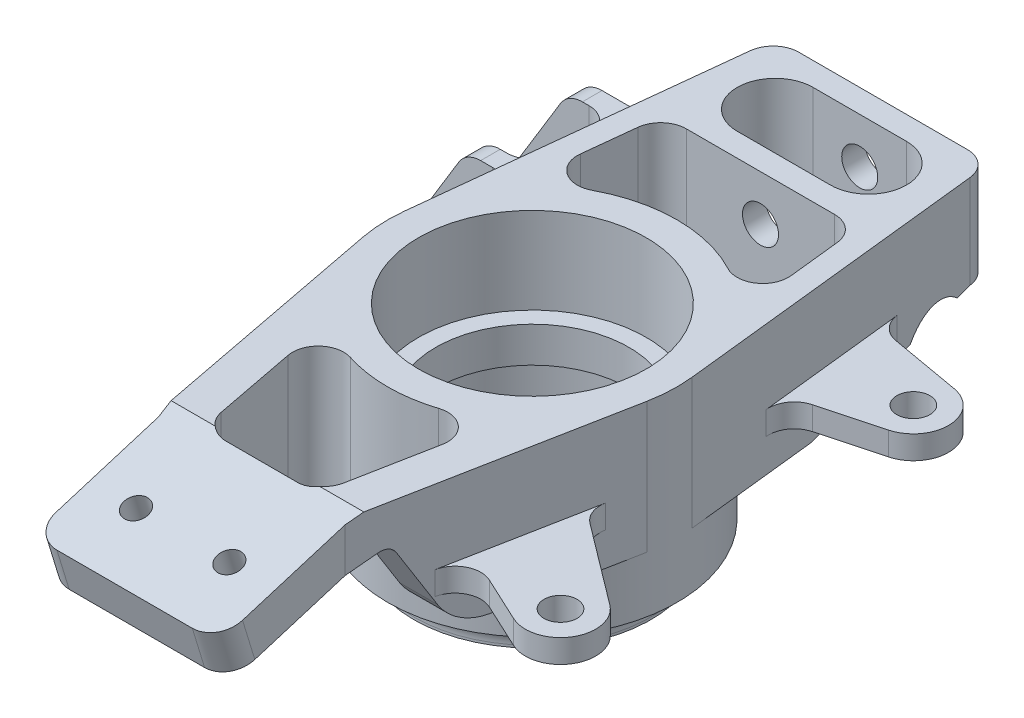
SolidWorks part; units mm, degrees
material "6061-T6 (SS)"
ref_plane "Front Plane" through (0, 0, 0) normal (0, 0, 1) x (1, 0, 0)
ref_plane "Top Plane" through (0, 0, 0) normal (0, 1, 0) x (1, 0, 0)
ref_plane "Right Plane" through (0, 0, 0) normal (1, 0, 0) x (0, 0, -1)
sketch "UBJ LBJ Geometry" plane through (0, 0, 0) normal (1, 0, 0) x (0, 0, -1)
  line L0 (0, 0) -> (0, -97.4059) construction
  line L1 (0, 0) -> (-30.7529, 0) construction
  line L2 (0, 22) -> (-45.5659, 22) construction
  line L3 (0, -10.5425) -> (-23.1063, -10.5425) construction
  line L4 (-84.7344, -51.66) -> (78.74, -22.958) construction
  line L5 (49.4563, 0) -> (49.4563, -88.2735) construction
  circle A0 centre (-84.7344, -51.66) radius 10.3251 construction
  circle A1 centre (78.74, -22.958) radius 10.3251 construction
  dimension "D7" = 20.6502
  dimension "D8" = 20.6502
  dimension "D1" = 22
  dimension "D2" = 32.5425
  dimension "D3" = 44.958
  dimension "D4" = 73.66
  dimension "D5" = 84.7344
  dimension "D6" = 78.74
  dimension "D9" = 29.2837
ref_plane "Wheel Face " through (0, 22, 0) normal (0, -1, 0) x (-1, 0, 0)
ref_plane "Upright Face" through (0, -10.5425, 0) normal (0, -1, 0) x (-1, 0, 0)
ref_plane "Tie Bracket Plane" through (0, 0, -49.4563) normal (0, 0, 1) x (1, 0, 0)
sketch "Tie Bracket Geometry" plane through (0, 0, -49.4563) normal (0, 0, 1) x (1, 0, 0)
  line L0 (0, -28.0995) -> (-60.5599, -51.7108) construction
  line L4 (0, 200000) -> (0, -200097.4059) construction
  circle A0 centre (-60.5599, -51.7108) radius 8.948 construction
  dimension "D1" = 65
  dimension "D2" = 68.7
sketch "Sketch1" plane through (0, 0, 0) normal (0, 0, 1) x (1, 0, 0)
  line L1 (-75.0953, -10.5425) -> (75.0953, -10.5425) construction
  line L2 (-39.37, -10.5425) -> (-39.37, -61.3425)
  line L3 (-39.37, -61.3425) -> (-32.258, -61.3425)
  line L4 (-32.258, -61.3425) -> (-32.258, -68.9625)
  line L5 (-32.258, -68.9625) -> (-30.9829, -68.9625)
  line L8 (-30.9829, -10.5425) -> (-30.9829, -34.0375)
  line L9 (-30.9829, -34.0375) -> (-26.289, -34.0375)
  line L10 (-26.289, -34.0375) -> (-26.289, -43.6895)
  line L11 (-26.289, -43.6895) -> (-30.9829, -43.6895)
  line L12 (-30.9829, -43.6895) -> (-30.9829, -68.9625)
  line L15 (-39.37, -10.5425) -> (-30.9829, -10.5425)
  line L17 (0, 0) -> (0, -23.5057) construction
  dimension "D1" = 9.652
  dimension "D2" = 61.9658
  dimension "D3" = 25.273
  dimension "D4" = 52.578
  dimension "D5" = 23.495
  dimension "D6" = 50.8
  dimension "D7" = 78.74
  dimension "D8" = 64.516
revolve "Bearing Housing Revolve" add sketch "Sketch1" angle 360 about L17
fillet "Bearing Housing Fillet" radius 6.985 1 edges at (0, -61.3425, 32.258)
sketch "Sketch2" plane through (0, -10.5425, 0) normal (0, -1, 0) x (-1, 0, 0)
  line L3 (39.37, -43.18) -> (39.37, 0)
  line L4 (-39.37, -43.18) -> (-39.37, 0)
  line L5 (39.37, -43.18) -> (-39.37, -43.18)
  circle A4 centre (0, 0) radius 39.37 construction
  arc A5 (39.37, 0) -> (-39.37, 0) centre (0, 0) cw
  dimension "D1" = 43.18
extrude "UBJ Prep" add sketch "Sketch2" along normal blind 35.56
sketch "Sketch3" plane through (-39.37, 0, 0) normal (-1, 0, 0) x (0, 0, 1)
  line L0 (-120.7672, 22) -> (120.7672, 22) construction
  line L1 (43.18, -10.5425) -> (72.0727, -10.5425)
  line L2 (72.0727, -10.5425) -> (110.937, -22.4245)
  line L3 (110.937, -22.4245) -> (107.5952, -33.355)
  line L4 (107.5952, -33.355) -> (68.7309, -21.473)
  line L6 (43.18, -46.1025) -> (43.18, -10.5425)
  line L7 (72.0727, -10.5425) -> (68.7309, -21.473) construction
  line L8 (104.3241, 12.415) -> (84.7344, -51.66) construction
  line L9 (55.2328, -39.1959) -> (64.6966, -23.0471)
  circle A0 centre (84.7344, -51.66) radius 12.7 construction
  arc A1 (43.18, -46.1025) -> (55.2328, -39.1959) centre (43.18, -32.1325) ccw
  arc A2 (68.7309, -21.473) -> (64.6966, -23.0471) centre (67.7098, -24.8129) ccw
  dimension "D7" = 6.985
  dimension "D8" = 27.94
  dimension "D9" = 25.4
  dimension "D1" = 73.66
  dimension "D2" = 84.7344
  dimension "D3" = 11.43
  dimension "D4" = 40.64
  dimension "D5" = 17
  dimension "D6" = 16.51
extrude "UBJ Extrude " add sketch "Sketch3" against normal up to surface (78.74 mm away) up to face at (39.37, -28.3225, 21.59)
sketch "Sketch4" plane through (0, -0.4206, -0.1286) normal (0, -0.9563, -0.2924) x (1, 0, 0)
  line L0 (0, 112.6458) -> (0, 27.8969) construction
  line L1 (39.37, 112.6458) -> (-39.37, 112.6458) construction
  line L3 (-12.7, 96.1358) -> (12.7, 96.1358) construction
  circle A0 centre (-12.7, 96.1358) radius 3.2639
  circle A1 centre (12.7, 96.1358) radius 3.2639
  point P8 (0, 96.1358)
  dimension "D2" = 6.5278
  dimension "D1" = 25.4
extrude "Camber Block Holes" cut sketch "Sketch4" against normal up to surface (11.43 mm away) up to face at (0, -16.4835, 91.5049)
sketch "Sketch5" plane through (0, -46.1025, 0) normal (0, -1, 0) x (1, 0, 0)
  line L0 (-25.4, 107.5952) -> (-25.4, 76.3532)
  line L1 (25.4, 110.937) -> (39.37, 110.937)
  line L2 (39.37, 107.5952) -> (-39.37, 107.5952) construction
  line L4 (-25.4, 76.3532) -> (-38.6608, 7.4393)
  line L5 (25.4, 107.5952) -> (25.4, 76.3532)
  line L6 (25.4, 76.3532) -> (38.6608, 7.4393)
  line L7 (-25.4, 107.5952) -> (-25.4, 110.937)
  line L8 (39.37, 110.937) -> (-39.37, 110.937) construction
  line L9 (25.4, 107.5952) -> (25.4, 110.937)
  line L10 (-25.4, 110.937) -> (-39.37, 110.937)
  line L11 (-39.37, 110.937) -> (-39.37, 0)
  line L12 (39.37, 110.937) -> (39.37, 0)
  line L13 (-15.5718, 73.66) -> (15.5718, 73.66)
  line L14 (-15.5718, 73.66) -> (-23.6959, 31.4404)
  line L15 (15.5718, 73.66) -> (23.6959, 31.4404)
  arc A0 (-39.37, 0) -> (-38.6608, 7.4393) centre (0, 0) cw
  circle A1 centre (0, 0) radius 39.37 construction
  arc A2 (39.37, 0) -> (-39.37, 0) centre (0, 0) ccw construction
  arc A3 (39.37, 0) -> (38.6608, 7.4393) centre (0, 0) ccw
  arc A4 (-23.6959, 31.4404) -> (23.6959, 31.4404) centre (0, 0) cw
  point P31 (0, 73.66)
  dimension "D1" = 25.4
  dimension "D2" = 10.16
  dimension "D3" = 31.242
  dimension "D4" = 73.66
extrude "Weight Saving" cut sketch "Sketch5" against normal through all
fillet "Fillet2" radius 6.985 4 edges at (23.6959, -28.3225, 31.4404) (-23.6959, -28.3225, 31.4404) (15.5718, -17.0039, 73.66) (-15.5718, -17.0039, 73.66)
sketch "Sketch6" plane through (0, -10.5425, 0) normal (0, -1, 0) x (-1, 0, 0)
  line L0 (-39.37, 0) -> (-39.37, 40.64)
  line L1 (-39.37, 40.64) -> (39.37, 40.64)
  line L2 (39.37, 40.64) -> (39.37, 0)
  circle A0 centre (0, 0) radius 39.37 construction
  arc A1 (-39.37, 0) -> (39.37, 0) centre (0, 0) cw
  dimension "D1" = 40.64
extrude "LBJ Prep" add sketch "Sketch6" along normal blind 35.56
sketch "Sketch8" plane through (-39.37, 0, 0) normal (-1, 0, 0) x (0, 0, 1)
  line L0 (-40.64, -10.5425) -> (-95.4151, -10.5425)
  line L1 (-95.4151, -10.5425) -> (-95.4151, -35.9425)
  line L2 (-95.4151, -35.9425) -> (-89.0651, -35.9425)
  line L7 (-40.64, -46.1025) -> (-40.64, -10.5425)
  line L8 (-120.7672, 22) -> (120.7672, 22) construction
  line L9 (-89.0651, -35.9425) -> (-89.0651, -10.5425) construction
  line L10 (-89.0651, -35.9425) -> (-40.64, -46.1025)
  circle A0 centre (-78.74, -22.958) radius 10.3251 construction
  dimension "D3" = 20.6502
  dimension "D1" = 78.74
  dimension "D2" = 44.958
  dimension "D4" = 6.35
  dimension "D5" = 25.4
extrude "LBJ Area " add sketch "Sketch8" against normal up to surface (78.74 mm away) up to face at (39.37, -28.3225, -20.32)
sketch "Sketch7" plane through (0, -46.1025, 0) normal (0, -1, 0) x (1, 0, 0)
  line L0 (-12.7, -78.74) -> (12.7, -78.74) construction
  line L1 (0, -200000) -> (0, 200045.5659) construction
  line L2 (-12.7, -68.4149) -> (12.7, -68.4149)
  line L3 (-12.7, -89.0651) -> (12.7, -89.0651)
  line L4 (-29.21, -95.4151) -> (-39.1385, -4.2631)
  line L5 (39.37, -95.4151) -> (-39.37, -95.4151) construction
  line L6 (29.21, -95.4151) -> (39.1385, -4.2631)
  line L7 (-29.21, -95.4151) -> (-39.37, -95.4151)
  line L8 (-39.37, -95.4151) -> (-39.37, 0)
  line L9 (29.21, -95.4151) -> (39.37, -95.4151)
  line L10 (39.37, -95.4151) -> (39.37, 0)
  line L13 (-26.455, -62.0649) -> (26.455, -62.0649)
  line L14 (26.455, -62.0649) -> (30.5043, -24.8895)
  line L15 (-26.455, -62.0649) -> (-30.5043, -24.8895)
  arc A0 (-12.7, -68.4149) -> (-12.7, -89.0651) centre (-12.7, -78.74) ccw
  arc A1 (12.7, -89.0651) -> (12.7, -68.4149) centre (12.7, -78.74) ccw
  circle A2 centre (0, 0) radius 39.37 construction
  arc A3 (-39.37, 0) -> (39.37, 0) centre (0, 0) ccw construction
  arc A4 (39.37, 0) -> (39.1385, -4.2631) centre (0, 0) cw
  arc A5 (-39.37, 0) -> (-39.1385, -4.2631) centre (0, 0) ccw
  arc A6 (-30.5043, -24.8895) -> (30.5043, -24.8895) centre (0, 0) ccw
  point P4 (0, -78.74)
  point P28 (0, -62.0649)
  dimension "D1" = 78.74
  dimension "D2" = 20.6502
  dimension "D3" = 25.4
  dimension "D4" = 10.16
  dimension "D5" = 6.35
  dimension "D6" = 6.35
extrude "LBJ Taper And Slot" cut sketch "Sketch7" against normal up to surface (35.56 mm away) up to face at (0, -10.5425, 30.9829)
fillet "Fillet3" radius 6.985 4 edges at (26.455, -26.0749, -62.0649) (-26.455, -26.0749, -62.0649) (30.5043, -28.3225, -24.8895) (-30.5043, -28.3225, -24.8895)
extrude "LBJ Holes 3/8 Close Fit Hole" cut sketch "Sketch9" against normal up to surface (33.3502 mm away) up to face at (0, -26.0749, -62.0649)
sketch "Sketch9" plane through (0, 0, -95.4151) normal (0, 0, -1) x (-1, 0, 0)
  circle A0 centre (0, -22.958) radius 4.9022
  dimension "D2" = 9.8044
  dimension "D1" = 22.958
ref_plane "Brake Mounting Plane" through (0, -30.7025, 0) normal (0, 1, 0) x (1, 0, 0)
sketch "Sketch10" plane through (0, -30.7025, 0) normal (0, 1, 0) x (1, 0, 0)
  line L0 (87.9814, 0) -> (161.3053, 0) construction
  line L1 (0, 72.9505) -> (0, 47.1638) construction
  line L2 (55.6514, 48) -> (55.6514, -48) construction
  line L3 (58.1309, 38.7464) -> (36.0276, 32.8239)
  line L4 (39.1385, 4.2631) -> (29.21, 95.4151) construction
  line L5 (36.0276, 32.8239) -> (32.8776, 61.7434)
  line L6 (32.8776, 61.7434) -> (57.3149, 57.4345)
  line L7 (61.4168, -40.3491) -> (36.0119, -21.2051)
  line L8 (26.2237, -72.0727) -> (38.6608, -7.4393) construction
  line L9 (36.0119, -21.2051) -> (31.031, -47.0897)
  line L10 (31.031, -47.0897) -> (51.6027, -56.6824)
  circle A0 centre (55.6514, 48) radius 4.5
  circle A1 centre (55.6514, -48) radius 4.5
  arc A2 (51.6027, -56.6824) -> (61.4168, -40.3491) centre (55.6514, -48) ccw
  arc A3 (58.1309, 38.7464) -> (57.3149, 57.4345) centre (55.6514, 48) ccw
  point P7 (55.6514, 0)
  dimension "D2" = 9
  dimension "D3" = 5.08
  dimension "D4" = 5.08
  dimension "D1" = 96
  dimension "D5" = 55.6514
  dimension "D6" = 80
  dimension "D7" = 75
  dimension "D8" = 53
  dimension "D9" = 65
extrude "Brake Mounts" add sketch "Sketch10" against normal blind 6.35
fillet "Fillet4" radius 6.985 4 edges at (36.0119, -33.8775, 21.2051) (31.031, -33.8775, 47.0897) (36.0276, -33.8775, -32.8239) (32.8776, -33.8775, -61.7434)
sketch "Sketch17" plane through (0, -37.0525, 0) normal (0, -1, 0) x (1, 0, 0)
  line L1 (36.8349, 16.928) -> (29.3384, 55.8861) construction
  line L3 (32.3099, -66.9555) -> (36.6761, -26.8705) construction
  line L6 (57.3149, -57.4345) -> (38.0409, -60.833) construction
  line L12 (61.4168, 40.3491) -> (39.4904, 23.8263) construction
  circle A0 centre (40.1682, 38.2515) radius 4.7625
  circle A1 centre (41.7635, -47.6031) radius 4.7625
  dimension "D1" = 9.525
  dimension "D2" = 9.525
  dimension "D3" = 2.54
  dimension "D4" = 2.54
  dimension "D5" = 7.62
  dimension "D6" = 6.35
extrude "rotor Cut " [suppressed] cut sketch "Sketch17" against normal up to surface (6.35 mm away) up to plane "Brake Mounting Plane"
sketch "Sketch16" plane through (0, -46.1025, 0) normal (0, 1, 0) x (1, 0, 0)
  line L0 (-38.6345, 8.89) -> (-55.7371, 8.89)
  line L1 (-38.6608, -7.4393) -> (-26.2237, -72.0727) construction
  line L2 (-55.7371, 8.89) -> (-55.7371, -8.89)
  line L3 (-55.7371, -8.89) -> (-38.3816, -8.89)
  line L5 (-29.21, 95.4151) -> (-39.1385, 4.2631) construction
  line L6 (-38.6345, 8.89) -> (-38.3816, -8.89)
  circle A0 centre (-46.609, 0) radius 5.9531
  point P8 (-55.7371, 0)
  dimension "D1" = 3.175
  dimension "D3" = 11.9062
  dimension "D2" = 46.609
  dimension "D4" = 17.78
extrude "Speed Sensor Mount" add sketch "Sketch16" along normal blind 5.08
fillet "Speed Sensor Fillet" radius 6.985 4 edges at (-55.7371, -43.5625, 8.89) (-55.7371, -43.5625, -8.89) (-38.3816, -43.5625, 8.89) (-38.6345, -43.5625, -8.89)
thread "15/32-32" pitch 0.9071 method cut profile "Thread Profile1" start angle 0, offset 1, length 10, pitch 0.7937, diameter 11.9062
ref_plane "Plane1" through (-40.6559, -45.1025, 0) normal (0, 0, 1) x (1, 0, 0)
sketch "Thread Profile1" plane through (-40.6559, -45.1025, 0) normal (0, 0, 1) x (1, 0, 0)
  line L0 (0, 0) -> (0, 0.9071) construction
  line L1 (0, 0) -> (0.491, 0.2835)
  line L2 (0.491, 0.2835) -> (0.491, 0.3969)
  line L3 (0.491, 0.3969) -> (0, 0.6804)
  line L4 (0.491, 0.3402) -> (0, 0.3402) construction
  line L11 (0, 0) -> (0, 0.6804)
  point P2 (0, 0)
  dimension "Pitch" = 0.9071
  dimension "Profile_Angle" = 60
  dimension "Profile_Land" = 0.1134
  dimension "Profile_Height" = 0.491
sketch "Sketch12" plane through (0, 0, -49.4563) normal (0, 0, 1) x (1, 0, 0)
  line L0 (0, 3.2946) -> (0, -38.5659) construction
  line L1 (-90.5661, 0) -> (-38.2005, 0) construction
  line L2 (-68.726, -10.5425) -> (-68.726, -51.7108)
  line L3 (-52.3938, -10.5425) -> (-52.3938, -51.7108)
  line L4 (-68.726, -10.5425) -> (-52.3938, -10.5425)
  line L6 (-75.0953, -10.5425) -> (75.0953, -10.5425) construction
  circle A0 centre (-60.5599, -51.7108) radius 3.2639
  arc A1 (-68.726, -51.7108) -> (-52.3938, -51.7108) centre (-60.5599, -51.7108) ccw
  dimension "D1" = 6.5278
  dimension "D2" = 4.9022
extrude "Initial Toe Bracket" add sketch "Sketch12" along normal blind 16.51 and the other way blind 16.51 separate body
sketch "Sketch13" plane through (-52.3938, 0, 0) normal (1, 0, 0) x (0, 0, -1)
  line L0 (32.9463, -16.8925) -> (65.9663, -16.8925)
  line L1 (65.9663, -51.7108) -> (65.9663, -10.5425) construction
  line L2 (65.9663, -16.8925) -> (65.9663, -38.4825)
  line L3 (32.9463, -16.8925) -> (32.9463, -38.4825)
  line L4 (200000, -10.5425) -> (-200023.1063, -10.5425) construction
  line L5 (32.9463, -38.4825) -> (65.9663, -38.4825)
  line L6 (32.9463, -51.7108) -> (32.9463, -10.5425) construction
  dimension "D1" = 6.35
  dimension "D2" = 21.59
extrude "Toe Bracket Connection to Upright" add sketch "Sketch13" along normal up to surface (19.9762 mm away) up to face at (-34.7109, -33.4025, -44.9123)
sketch "Sketch14" plane through (0, 0, -65.9663) normal (0, 0, -1) x (-1, 0, 0)
  line L0 (52.3938, -16.8925) -> (68.726, -16.8925)
  line L1 (68.726, -10.5425) -> (68.726, -51.7108) construction
  line L2 (68.726, -16.8925) -> (68.726, -10.5425)
  line L3 (68.726, -10.5425) -> (52.3938, -10.5425)
  line L4 (52.3938, -10.5425) -> (52.3938, -16.8925)
extrude "Excess Toe Bracket Cut" cut sketch "Sketch14" against normal up to surface (33.02 mm away) up to face at (-52.382, -30.4278, -32.9463)
sketch "Sketch19" plane through (0, 0, -32.9463) normal (0, 0, 1) x (1, 0, 0)
  line L0 (-53.5754, -55.9418) -> (-42.9993, -38.4825)
  line L1 (-42.9993, -38.4825) -> (-52.3938, -38.4825)
  line L2 (-52.3938, -38.4825) -> (-53.5754, -55.9418)
  line L3 (-36.0143, -38.4825) -> (-52.3938, -38.4825) construction
  line L4 (-36.0143, -16.8925) -> (-36.0143, -38.4825) construction
  arc A0 (-68.726, -51.7108) -> (-52.3938, -51.7108) centre (-60.5599, -51.7108) ccw construction
  dimension "D1" = 6.985
extrude "Adding To Toe" add sketch "Sketch19" against normal up to surface (33.02 mm away) up to face at (-51.1792, -37.0563, -65.9663)
sketch "Sketch20" plane through (0, 0, -32.9463) normal (0, 0, 1) x (1, 0, 0)
  line L0 (-50.946, -16.8925) -> (-68.726, -16.8925)
  line L1 (-36.0143, -16.8925) -> (-68.726, -16.8925) construction
  line L2 (-68.726, -16.8925) -> (-68.726, -46.1025)
  line L3 (-68.726, -16.8925) -> (-68.726, -51.7108) construction
  line L4 (-68.726, -46.1025) -> (-50.946, -16.8925)
  dimension "D1" = 17.78
  dimension "D2" = 29.21
extrude "Cut-Extrude1" cut sketch "Sketch20" against normal up to surface (33.02 mm away) up to face at (-50.0779, -37.3587, -65.9663)
sketch "Sketch15" plane through (-68.726, 0, 0) normal (-1, 0, 0) x (0, 0, 1)
  line L0 (-60.6323, -16.8925) -> (-38.2803, -16.8925)
  line L1 (-38.2803, -16.8925) -> (-38.2803, -59.8769)
  line L2 (-65.9663, -59.8769) -> (-32.9463, -59.8769) construction
  line L3 (-38.2803, -59.8769) -> (-60.6323, -59.8769)
  line L4 (-60.6323, -59.8769) -> (-60.6323, -16.8925)
  line L6 (-49.4563, -25.7825) -> (-49.4563, -39.109) construction
  line L8 (-32.9463, -16.8925) -> (-65.9663, -16.8925) construction
  point P9 (-49.4563, -16.8925)
  point P11 (-49.4563, -16.8925)
  dimension "D1" = 22.352
extrude "Toe Bracket Slot" cut sketch "Sketch15" against normal blind 30.48
fillet "Toe Bracket Fillet" radius 6.985 2 edges at (-32.4176, -27.6875, -65.9663) (-36.0143, -27.6875, -32.9463)
fillet "Fillet7" radius 6.985 4 edges at (-68.726, -46.1025, -35.6133) (-68.726, -46.1025, -63.2993) (-50.946, -16.8925, -63.2993) (-50.946, -16.8925, -35.6133)
fillet "Inside Toe Fillet" radius 6.985 2 edges at (-38.246, -27.6875, -38.2803) (-38.246, -27.6875, -60.6323)
fillet "Outside Fillets" radius 6.985 4 edges at (-25.4, -27.8897, 109.2661) (25.4, -27.8897, 109.2661) (29.21, -23.2425, -95.4151) (-29.21, -23.2425, -95.4151)
sketch "Angle Reference" plane through (0, 0, -95.4151) normal (0, 0, -1) x (-1, 0, 0)
  line L0 (0, -22.958) -> (32.5253, -73.0426) construction
  line L1 (0, 0) -> (0, -88.2735) construction
  line L2 (0, -22.958) -> (69.6053, -82.0294) construction
  dimension "D1" = 33
  dimension "D2" = 16.68
ref_plane "Plane2" through (0, -22.958, -78.74) normal (-0.7624, -0.6471, 0) x (0, 0, 1)
sketch "Sketch22" plane through (0, -22.958, -78.74) normal (-0.7624, -0.6471, 0) x (0, 0, 1)
  line L0 (0, 1.0566) -> (0, -4.2774) construction
  line L3 (10.3251, 1.0566) -> (10.3251, -4.2774)
  line L4 (-10.3251, 1.0566) -> (-10.3251, -4.2774)
  arc A2 (10.3251, 1.0566) -> (-10.3251, 1.0566) centre (0, 1.0566) ccw
  arc A3 (-10.3251, -4.2774) -> (10.3251, -4.2774) centre (0, -4.2774) ccw
  point P2 (0, -1.6104)
  dimension "D1" = 20.6502
  dimension "D2" = 1.0566
  dimension "D3" = 5.334
extrude "Angle Slot Cut" cut sketch "Sketch22" along normal through all
mirror "Mirror1" about plane through (0, 0, 0) normal (1, 0, 0) of "Angle Slot Cut"
equation "\"Wheel_Offset\"= 22mm"
equation "\"HUB_to_UBJ_Lat\"= 2.9in"
equation "\"Hub_to_UBJ_Vert\"= 3.336in"
equation "\"Hub_to_LBJ_Lat\"= 1.77in"
equation "\"Hub_to_LBJ_Vert\"= 3.1in"
equation "\"Wheel_face_to_Upright_back\"= 1.2812in'This is the distance between the whee face to the upright back."
equation "\"UBJ_Angle\"= 17deg"
equation "\"D2@UBJ LBJ Geometry\" = \"Wheel_face_to_Upright_back\""
equation "\"D3@UBJ LBJ Geometry\" = \"Hub_to_LBJ_Lat\""
equation "\"D4@UBJ LBJ Geometry\" = \"HUB_to_UBJ_Lat\""
equation "\"D5@UBJ LBJ Geometry\" = \"Hub_to_UBJ_Vert\""
equation "\"D6@UBJ LBJ Geometry\" = \"Hub_to_LBJ_Vert\""
equation "\"D1@Sketch3\"=\"HUB_to_UBJ_Lat\""
equation "\"D2@Sketch3\"=\"Hub_to_UBJ_Vert\""
equation "\"D1@Sketch8\"=\"Hub_to_LBJ_Vert\""
equation "\"D2@Sketch8\"=\"Hub_to_LBJ_Lat\""
equation "\"Hub_Tie_Bracket_Vert\"= 2in'(Not Given) Ask Sus and Controls later"
equation "\"Tie_Beta\"= 21.3deg'From FE11 Master "
equation "\"Toe_Arm\"= 65mm'From FE11 Master (Assume Dist start at KPI)"
equation "\"D1@Sketch7\"=\"Hub_to_LBJ_Vert\""
equation "\"D1@Sketch9\"=\"Hub_to_LBJ_Lat\"-\"Wheel_Offset\""
equation "\"D1@Tie Bracket Geometry\" = \"Toe_Arm\""
equation "\"D2@Tie Bracket Geometry\" = 90 - \"Tie_Beta\""
equation "\"oranizeBlock\"= 0"
equation "\"BrakeAngle\"= 65deg"
equation "\"D5@Sketch3\"=\"UBJ_Angle\""
equation "\"D1@Sketch7\"=\"Hub_to_LBJ_Lat\""
